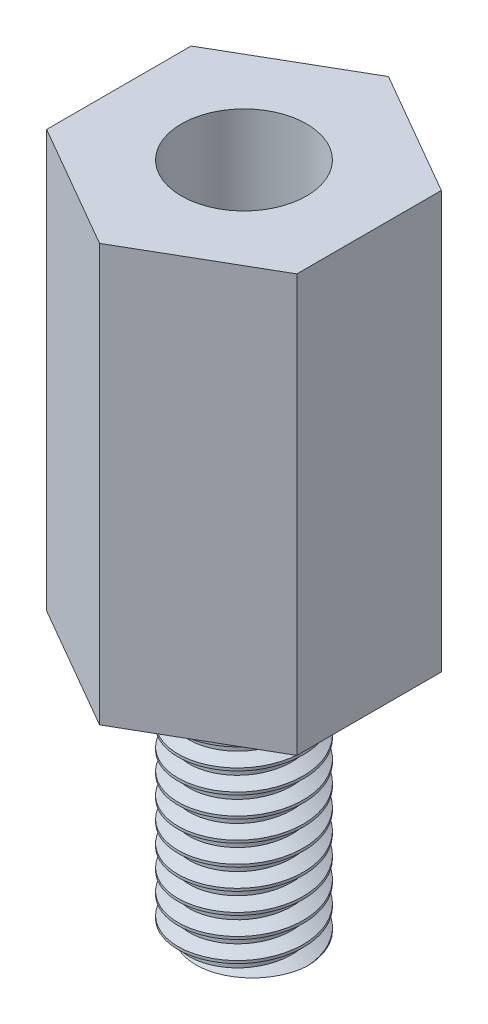
SolidWorks part; units mm, degrees
material "Copper"
ref_plane "Front Plane" through (0, 0, 0) normal (0, 0, 1) x (1, 0, 0)
ref_plane "Top Plane" through (0, 0, 0) normal (0, 1, 0) x (1, 0, 0)
ref_plane "Right Plane" through (0, 0, 0) normal (1, 0, 0) x (0, 0, -1)
sketch "Sketch1" plane through (0, 0, 0) normal (0, 1, 0) x (1, 0, 0)
  line L1 (3, 1.7321) -> (0, 3.4641)
  line L2 (0, 3.4641) -> (-3, 1.7321)
  line L3 (-3, 1.7321) -> (-3, -1.7321)
  line L4 (-3, -1.7321) -> (0, -3.4641)
  line L5 (0, -3.4641) -> (3, -1.7321)
  line L6 (3, -1.7321) -> (3, 1.7321)
  circle A0 centre (0, 0) radius 3 construction
  dimension "D1" = 6
extrude "Boss-Extrude1" add sketch "Sketch1" along normal blind 25 contours L2 L3 L4 L5 L6 L1
sketch "Sketch2" plane through (0, 0, 0) normal (0, -1, 0) x (1, 0, 0)
  circle A0 centre (0, 0) radius 1.5
  dimension "D1" = 3
extrude "Boss-Extrude2" add sketch "Sketch2" along normal blind 6
hole_wizard "Tap Drill for M3 Tap1" positions "Sketch3" profile "Sketch4" hole size "M3" standard "ISO"
sketch "Sketch3" plane through (0, 25, 0) normal (0, 1, 0) x (1, 0, 0)
  point P0 (0, 0)
sketch "Sketch4" plane through (0, 25, 0) normal (1, 0, 0) x (0, 0, 1)
  line L0 (0, 0) -> (0, 10.7511)
  line L1 (0, 10.7511) -> (1.25, 10)
  line L2 (1.25, 10) -> (1.25, 0)
  line L5 (1.25, 0) -> (0, 0)
  line L10 (0, 10.7511) -> (-1.25, 10) construction
  line L11 (0, -6.35) -> (0, 107.95) construction
  dimension "Hole Dia." = 2.5
  dimension "Hole Depth" = 10
  dimension "Drill Angle" = 118
thread "Thread1" pitch 0.5 method cut trim with start face yes profile "Thread Profile1" start angle 0, offset 1, length 9, pitch 0.5, diameter 2.5
ref_plane "Plane1" through (-1.25, 26, 0) normal (0, 0, 1) x (-1, 0, 0)
sketch "Thread Profile1" plane through (-1.25, 26, 0) normal (0, 0, 1) x (-1, 0, 0)
  line L0 (0, 0) -> (0, 0.5) construction
  line L1 (0, 0) -> (0.2706, 0.1562)
  line L2 (0.2706, 0.1562) -> (0.2706, 0.2187)
  line L3 (0.2706, 0.2187) -> (0, 0.375)
  line L4 (0.2706, 0.1875) -> (0, 0.1875) construction
  line L11 (0, 0) -> (0, 0.375)
  point P2 (0, 0)
  dimension "Pitch" = 0.5
  dimension "Profile_Angle" = 60
  dimension "Profile_Land" = 0.0625
  dimension "Profile_Height" = 0.2706
thread "Thread2" pitch 0.5 method cut profile "Thread Profile2" start angle 0, offset 1, length 6.5, pitch 0.5, diameter 3
ref_plane "Plane2" through (1.5, -7, 0) normal (0, 0, 1) x (1, 0, 0)
sketch "Thread Profile2" plane through (1.5, -7, 0) normal (0, 0, 1) x (1, 0, 0)
  line L0 (0, 0) -> (0, 0.5) construction
  line L11 (0, 0) -> (0, 0.4375)
  line L12 (0, 0.4375) -> (-0.2706, 0.2812)
  line L13 (-0.2706, 0.2812) -> (-0.2706, 0.1562)
  line L15 (-0.2706, 0.1562) -> (0, 0)
  line L17 (-0.2706, 0.2187) -> (0, 0.2187) construction
  point P2 (0, 0)
  dimension "Pitch" = 0.5
  dimension "Profile_Angle" = 60
  dimension "Profile_Land" = 0.125
  dimension "Profile_Height" = 0.2706
sketch "Sketch9" plane through (0, 0, 0) normal (0, 1, 0) x (1, 0, 0)
  circle A0 centre (0, 0) radius 1.225
  dimension "D1" = 2.45
extrude "Cut-Extrude-Thin1" cut sketch "Sketch9" against normal blind 0.5 thin contours A0 thin type one direction wall 10
sketch "Sketch10" plane through (0, 25, 0) normal (0, 1, 0) x (1, 0, 0)
  circle A0 centre (0, 0) radius 3.7812
extrude "Cut-Extrude1" cut sketch "Sketch10" against normal blind 15
sketch "Sketch11" plane through (0, 10, 0) normal (0, 1, 0) x (1, 0, 0)
  circle A0 centre (0, 0) radius 1.5
  dimension "D1" = 3
extrude "Cut-Extrude2" cut sketch "Sketch11" against normal blind 7
